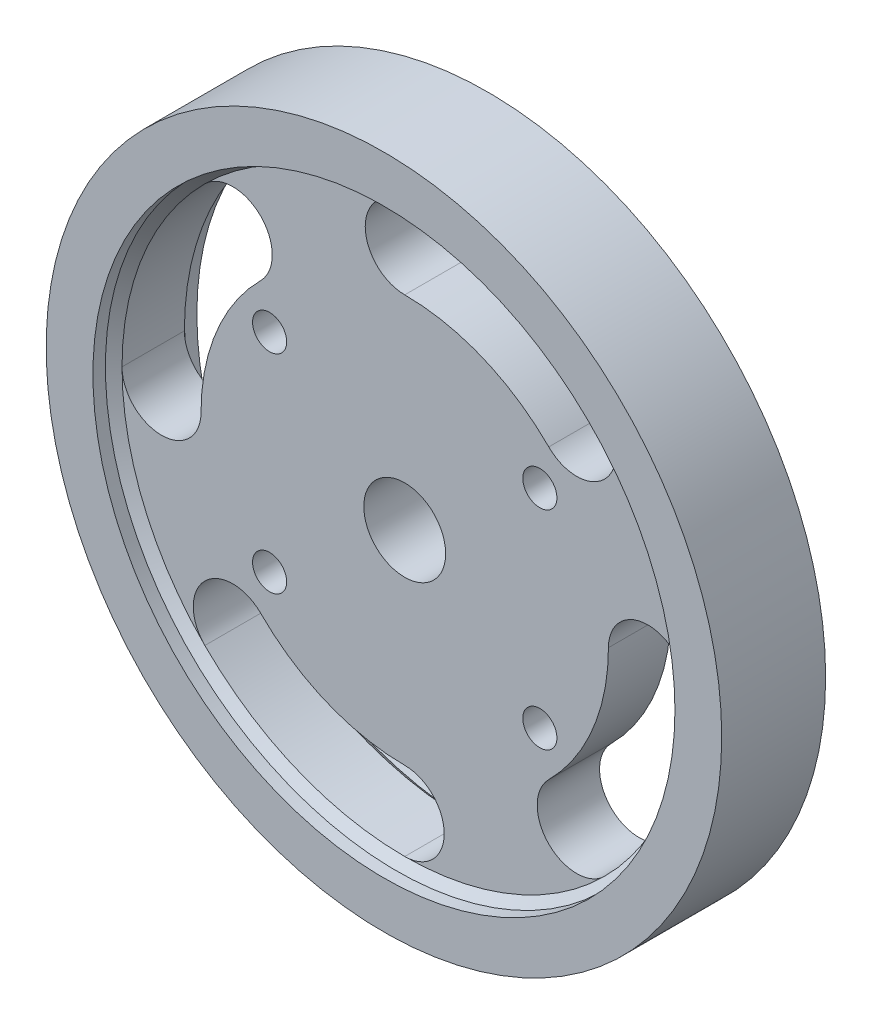
SolidWorks part; units mm, degrees
ref_plane "Front Plane" through (0, 0, 0) normal (0, 0, 1) x (1, 0, 0)
ref_plane "Top Plane" through (0, 0, 0) normal (0, 1, 0) x (1, 0, 0)
ref_plane "Right Plane" through (0, 0, 0) normal (1, 0, 0) x (0, 0, -1)
sketch "Sketch1" plane through (0, 0, 0) normal (0, 0, 1) x (1, 0, 0)
  circle A0 centre (0, 0) radius 20.6375
  dimension "D1" = 41.275
extrude "Base" add sketch "Sketch1" along normal blind 6.35
ref_axis "Axis1" through (0, 0, 19.5503) along (0, 0, -1)
sketch "Sketch3" plane through (0, 0, 0) normal (0, 0, -1) x (-1, 0, 0)
  circle A0 centre (0, 0) radius 3.937
  dimension "D1" = 7.874
extrude "Boss-Extrude2" add sketch "Sketch3" along normal blind 3.81
sketch "Sketch2" plane through (0, 0, 0) normal (0, 0, 1) x (1, 0, 0)
  circle A0 centre (0, 0) radius 2.5
  dimension "D1" = 5
extrude "Cut-Extrude2" cut sketch "Sketch2" along normal through all and the other way through all
sketch "Sketch5" plane through (0, 0, 0) normal (0, 0, 1) x (1, 0, 0)
  line L0 (0, 0) -> (12.2131, 12.2131) construction
  line L1 (0, 0) -> (0, 17.272) construction
  circle A0 centre (0, 0) radius 12.446 construction
  arc A1 (8.8007, 8.8007) -> (0, 12.446) centre (0, 0) ccw
  arc A2 (12.2131, 12.2131) -> (0, 17.272) centre (0, 0) ccw
  arc A3 (8.8007, 8.8007) -> (12.2131, 12.2131) centre (10.5069, 10.5069) ccw
  arc A4 (0, 12.446) -> (0, 17.272) centre (0, 14.859) cw
  dimension "D1" = 24.892
  dimension "D3" = 4.826
  dimension "D2" = 45
extrude "Cut-Extrude3" cut sketch "Sketch5" along normal through all
sketch "Sketch7" plane through (0, 0, 0) normal (0, 0, -1) x (-1, 0, 0)
  circle A0 centre (0, 0) radius 12.446
  circle A1 centre (0, 0) radius 17.78
  arc A2 (0, 12.446) -> (-8.8007, 8.8007) centre (0, 0) ccw construction
  dimension "D1" = 35.56
extrude "Cut-Extrude4" cut sketch "Sketch7" against normal blind 1.27
chamfer "Chamfer1" distance 0.508 angle 45 1 edges at (-17.78, 0, 1.27)
chamfer "Chamfer2" distance 1.27 angle 45 1 edges at (12.446, 0, 0)
chamfer "Chamfer3" distance 0.254 angle 45 1 edges at (-3.937, 0, -3.81)
sketch "Sketch8" plane through (0, 0, 6.35) normal (0, 0, 1) x (1, 0, 0)
  circle A0 centre (0, 0) radius 17.78
  dimension "D1" = 35.56
extrude "Cut-Extrude5" cut sketch "Sketch8" against normal blind 1.27
chamfer "Chamfer4" distance 0.508 angle 45 1 edges at (17.78, 0, 5.08)
sketch "Sketch9" plane through (0, 0, 0) normal (0, 0, -1) x (-1, 0, 0)
  line L1 (-8.255, -6.35) -> (8.255, -6.35) construction
  line L2 (-8.255, -6.35) -> (-8.255, 6.35) construction
  line L3 (-8.255, 6.35) -> (8.255, 6.35) construction
  line L4 (8.255, -6.35) -> (8.255, 6.35) construction
  line L5 (-8.255, -6.35) -> (8.255, 6.35) construction
  line L6 (-8.255, 6.35) -> (8.255, -6.35) construction
  circle A0 centre (-8.255, 6.35) radius 1.0414
  circle A1 centre (8.255, 6.35) radius 1.0414
  circle A2 centre (8.255, -6.35) radius 1.0414
  circle A3 centre (-8.255, -6.35) radius 1.0414
  point P8 (0, 0)
  dimension "D3" = 2.0828
  dimension "D1" = 16.51
  dimension "D2" = 12.7
extrude "Cut-Extrude6" cut sketch "Sketch9" against normal through all
sketch "Sketch10" plane through (0, 0, 0) normal (0, 0, -1) x (-1, 0, 0)
  line L0 (-9.2229, 5.0917) -> (-9.7365, 5.4867) construction
  line L1 (-10.2295, 5.866) -> (-8.2937, 8.3826) construction
  line L2 (-9.7365, 5.4867) -> (-10.2295, 5.866) construction
  line L3 (-7.2871, 7.6083) -> (-7.8006, 8.0033) construction
  line L4 (-7.8006, 8.0033) -> (-8.2937, 8.3826) construction
  line L5 (7.2871, 7.6083) -> (7.8006, 8.0033)
  line L6 (8.2937, 8.3826) -> (10.2295, 5.866)
  line L7 (7.8006, 8.0033) -> (8.2937, 8.3826)
  line L8 (9.2229, 5.0917) -> (9.7365, 5.4867)
  line L9 (9.7365, 5.4867) -> (10.2295, 5.866)
  line L10 (9.2229, -5.0917) -> (9.7365, -5.4867)
  line L11 (10.2295, -5.866) -> (8.2937, -8.3826)
  line L12 (9.7365, -5.4867) -> (10.2295, -5.866)
  line L13 (7.2871, -7.6083) -> (7.8006, -8.0033)
  line L14 (7.8006, -8.0033) -> (8.2937, -8.3826)
  line L15 (-7.2871, -7.6083) -> (-7.8006, -8.0033)
  line L16 (-8.2937, -8.3826) -> (-10.2295, -5.866)
  line L17 (-7.8006, -8.0033) -> (-8.2937, -8.3826)
  line L18 (-9.2229, -5.0917) -> (-9.7365, -5.4867)
  line L19 (-9.7365, -5.4867) -> (-10.2295, -5.866)
  arc A0 (-9.2229, 5.0917) -> (-7.2871, 7.6083) centre (-8.255, 6.35) ccw construction
  arc A1 (-8.3905, -7.3825) -> (-9.2878, -6.2161) centre (-8.255, -6.35) ccw construction
  arc A2 (-9.2878, 6.2161) -> (-9.2878, -6.2161) centre (0, 0) ccw construction
  arc A3 (9.2878, -6.2161) -> (9.2878, 6.2161) centre (0, 0) ccw construction
  arc A4 (8.3905, 7.3825) -> (-8.3905, 7.3825) centre (0, 0) ccw construction
  arc A5 (7.2871, 7.6083) -> (9.2229, 5.0917) centre (8.255, 6.35) ccw
  arc A6 (9.2229, -5.0917) -> (7.2871, -7.6083) centre (8.255, -6.35) ccw
  arc A7 (-7.2871, -7.6083) -> (-9.2229, -5.0917) centre (-8.255, -6.35) ccw
  arc A8 (8.3905, 7.3825) -> (9.2878, 6.2161) centre (8.255, 6.35) ccw construction
  arc A9 (-8.3905, -7.3825) -> (8.3905, -7.3825) centre (0, 0) ccw construction
  arc A10 (9.2878, -6.2161) -> (8.3905, -7.3825) centre (8.255, -6.35) ccw construction
  dimension "D1" = 3.175
  dimension "D4" = 3.175
  dimension "D7" = 3.175
  dimension "D10" = 3.175
  dimension "D2" = 3.175
  dimension "D3" = 1.27
  dimension "D5" = 3.175
  dimension "D6" = 1.27
  dimension "D8" = 3.175
  dimension "D9" = 1.27
  dimension "D11" = 3.175
  dimension "D12" = 1.27
extrude "Cut-Extrude7" cut sketch "Sketch10" against normal blind 0.381
pattern_circular "CirPattern1" count 4 over 360 about axis through (0, 0, 19.5503) along (0, 0, -1) of "Cut-Extrude3"
